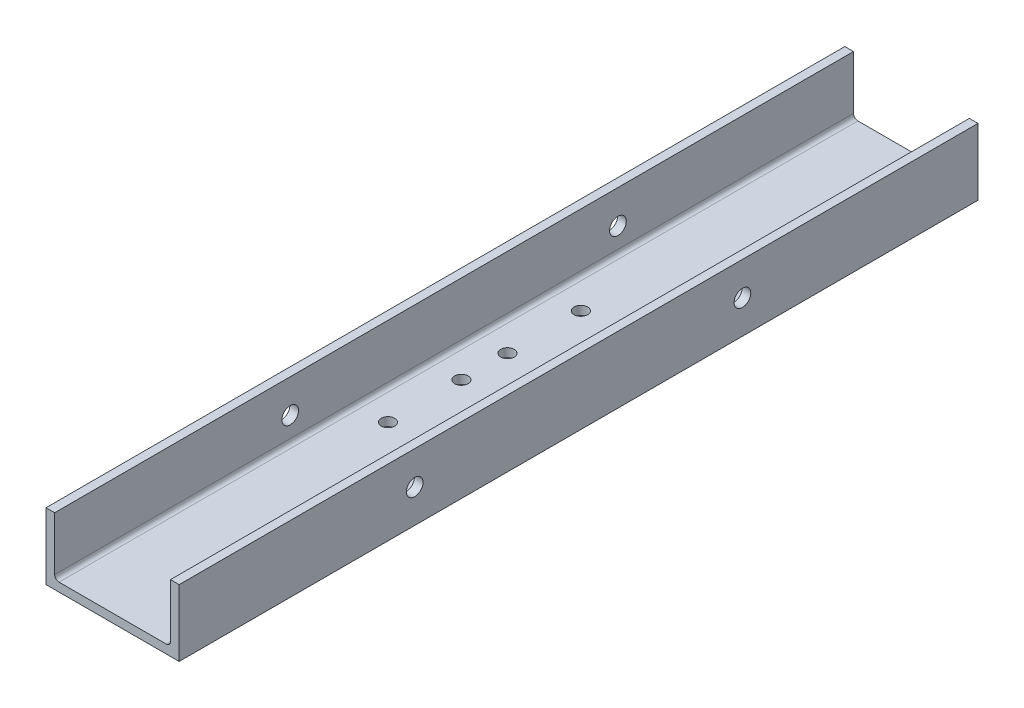
SolidWorks part; units mm, degrees
ref_plane "Front Plane" through (0, 0, 0) normal (0, 0, 1) x (1, 0, 0)
ref_plane "Top Plane" through (0, 0, 0) normal (0, 1, 0) x (1, 0, 0)
ref_plane "Right Plane" through (0, 0, 0) normal (1, 0, 0) x (0, 0, -1)
sketch "Sketch1" plane through (0, 0, 0) normal (0, 0, 1) x (1, 0, 0)
  line L0 (-25.4, 12.7) -> (-25.4, -12.7) construction
  line L1 (-25.4, -12.7) -> (25.4, -12.7) construction
  line L2 (25.4, -12.7) -> (25.4, 12.7) construction
  line L3 (22.098, -9.398) -> (-22.098, -9.398) construction
  line L4 (-22.098, -9.398) -> (-22.098, 12.7) construction
  line L6 (-22.098, 12.7) -> (-25.4, 12.7) construction
  line L7 (0, -12.7) -> (0, 0) construction
  line L8 (25.4, 12.7) -> (22.098, 12.7) construction
  line L9 (22.098, 12.7) -> (22.098, -9.398) construction
  line L10 (0, -9.398) -> (0, -12.7) construction
  point P4 (0, 0)
  point P11 (25.4, -9.398)
  dimension "Outside Height" = 25.4
  dimension "Outside Width" = 50.8
  dimension "Leg Thickness" = 3.302
  dimension "D1" = 12.7
  dimension "Inside Height" = 22.098
  dimension "Inside Width" = 44.196
  dimension "Base Thickness" = 3.302
sketch "Sketch2" plane through (0, 0, 0) normal (1, 0, 0) x (0, 0, -1)
  line L0 (210.695, 12.7) -> (-210.695, 12.7) construction
  line L1 (0, -9.398) -> (0, 12.7) construction
  point P0 (-159.895, 12.7)
  point P4 (0, 12.7)
  point P6 (159.895, 12.7)
  dimension "D1" = 50.8
  dimension "D2" = 50.8
  dimension "Length" = 421.39
sketch "Sketch3" plane through (0, 0, 0) normal (0, 0, 1) x (1, 0, 0)
  line L6 (-25.4, 12.7) -> (-25.4, -12.7)
  line L7 (-25.4, -12.7) -> (25.4, -12.7)
  line L8 (25.4, -12.7) -> (25.4, 12.7)
  line L9 (25.4, 12.7) -> (22.098, 12.7)
  line L10 (22.098, 12.7) -> (22.098, -9.398)
  line L11 (22.098, -9.398) -> (-22.098, -9.398)
  line L12 (-22.098, -9.398) -> (-22.098, 12.7)
  line L13 (-22.098, 12.7) -> (-25.4, 12.7)
extrude "Boss-Extrude1" add sketch "Sketch3" along normal mid plane 304.8
fillet "Fillet1" radius 1.651 2 edges at (22.098, -9.398, 0) (-22.098, -9.398, 0)
sketch "Sketch4" plane through (0, -9.398, 0) normal (0, 1, 0) x (1, 0, 0)
  line L0 (0, 152.4) -> (0, -152.4) construction
  line L1 (20.447, 152.4) -> (-20.447, 152.4) construction
  line L2 (20.447, -152.4) -> (-20.447, -152.4) construction
  line L3 (-23.5304, 0) -> (23.5304, 0) construction
  circle A0 centre (-10.5304, 8.79) radius 2.585
  circle A1 centre (10.4696, 8.79) radius 2.585
  circle A2 centre (-10.5304, 36.79) radius 2.585
  circle A3 centre (10.4696, 36.79) radius 2.585
  circle A4 centre (-10.5304, -36.79) radius 2.585
  circle A5 centre (10.4696, -36.79) radius 2.585
  circle A6 centre (10.4696, -8.79) radius 2.585
  circle A7 centre (-10.5304, -8.79) radius 2.585
  point P24 (0, 0)
  point P26 (0, 0)
  dimension "D1" = 5.17
  dimension "D2" = 5.17
  dimension "D3" = 28
  dimension "D4" = 8.79
  dimension "D5" = 8.79
  dimension "D6" = 28
extrude "Cut-Extrude1" cut sketch "Sketch4" against normal blind 10
sketch "Sketch5" plane through (0, -9.398, 0) normal (0, 1, 0) x (1, 0, 0)
  circle A0 centre (0, 62.5214) radius 3.18
  circle A2 centre (0, -62.52) radius 3.18
  circle A3 centre (-10.5304, -8.79) radius 2.585 construction
  dimension "D1" = 53.73
  dimension "D2" = 6.36
sketch "Sketch9" plane through (0, 0, 0) normal (1, 0, 0) x (0, 0, -1)
  line L0 (0, 0) -> (0, -12.7) construction
  line L1 (-152.4, -12.7) -> (152.4, -12.7) construction
  line L2 (0, 0) -> (-95.1707, 0) construction
  circle A0 centre (-62.52, 0) radius 3.18
  circle A1 centre (62.52, 0) radius 3.18
  dimension "D2" = 6.36
  dimension "D1" = 62.52
extrude "Cut-Extrude2" cut sketch "Sketch9" against normal mid plane 60
equation "\"D1@Boss-Extrude1\"=\"Length@Sketch2\""
equation "\"D2@Sketch2\"=\"D1@Sketch2\""
equation "\"D1@Sketch1\"=\"Outside Height@Sketch1\"/2"
equation "\"D1@Fillet1\"=\"Leg Thickness@Sketch1\"*.5"
equation "\"D1@Sketch2\"=\"Outside Width@Sketch1\"*1"
